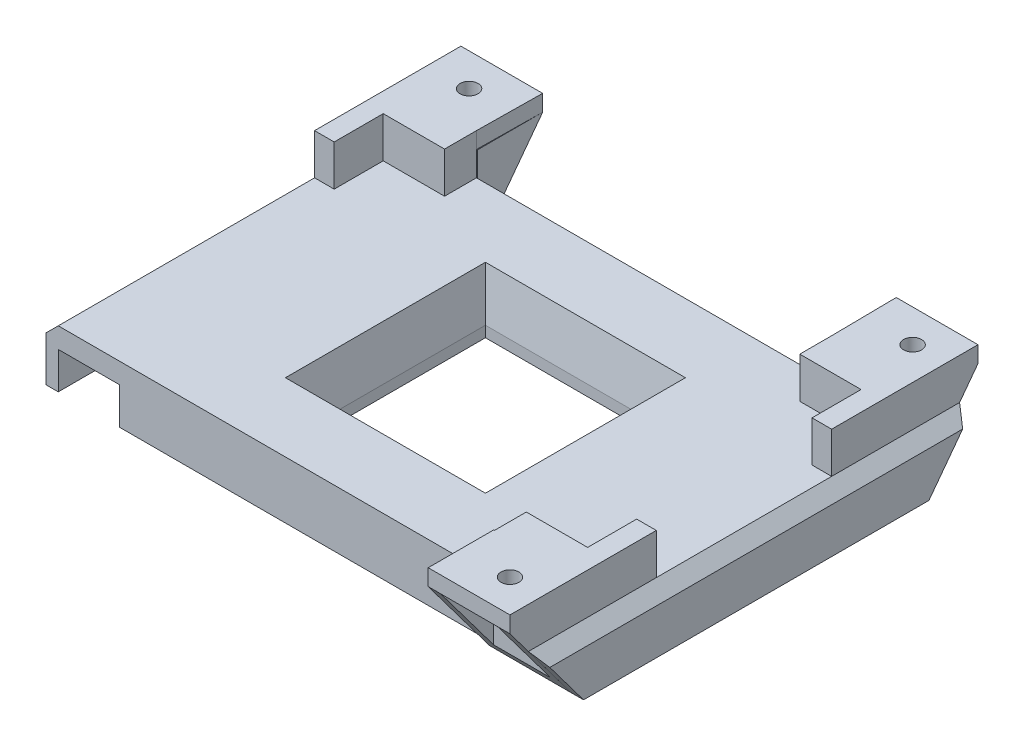
SolidWorks part; units mm, degrees
ref_plane "Спереди" through (0, 0, 0) normal (0, 0, 1) x (1, 0, 0)
ref_plane "Сверху" through (0, 0, 0) normal (0, 1, 0) x (1, 0, 0)
ref_plane "Справа" through (0, 0, 0) normal (1, 0, 0) x (0, 0, -1)
ref_plane "Плоскость4" through (0, 122.196, 0) normal (0, 1, 0) x (1, 0, 0)
sketch "Эскиз1" plane through (0, 122.196, 0) normal (0, 1, 0) x (1, 0, 0)
  line L0 (16.559, -48.2731) -> (16.559, -54.2731)
  line L1 (16.559, -54.2731) -> (7.559, -63.2731)
  line L2 (1.559, -63.2731) -> (7.559, -63.2731) construction
  line L3 (7.559, -63.2731) -> (1.559, -63.2731)
  line L4 (1.559, -63.2731) -> (1.559, -115.7731)
  line L5 (1.559, -115.7731) -> (7.559, -115.7731)
  line L6 (16.559, -124.7731) -> (7.559, -115.7731) construction
  line L7 (7.559, -115.7731) -> (1.559, -115.7731) construction
  line L8 (7.559, -115.7731) -> (16.559, -124.7731)
  line L9 (16.559, -124.7731) -> (16.559, -130.7731)
  line L10 (-8.25, -130.7731) -> (8.25, -130.7731) construction
  line L11 (16.559, -130.7731) -> (16.559, -124.7731) construction
  line L12 (16.559, -130.7731) -> (113.059, -130.7731)
  line L13 (113.059, -130.7731) -> (113.059, -124.7731)
  line L14 (113.059, -124.7731) -> (122.059, -115.7731)
  line L15 (122.059, -115.7731) -> (128.059, -115.7731)
  line L16 (128.059, -115.7731) -> (128.059, -63.2731)
  line L17 (128.059, -63.2731) -> (122.059, -63.2731)
  line L18 (122.059, -63.2731) -> (113.059, -54.2731)
  line L19 (113.059, -54.2731) -> (113.059, -48.2731)
  line L20 (113.059, -48.2731) -> (16.559, -48.2731)
  line L21 (42.3449, -67.059) -> (42.3449, -111.9872)
  line L22 (42.3449, -111.9872) -> (87.2731, -111.9872)
  line L23 (87.2731, -111.9872) -> (87.2731, -67.059)
  line L24 (87.2731, -67.059) -> (42.3449, -67.059)
extrude "Бобышка-Вытянуть1" add sketch "Эскиз1" along normal blind 9
ref_plane "Плоскость5" through (0, 131.196, 0) normal (0, 1, 0) x (1, 0, 0)
sketch "Эскиз2" plane through (0, 131.196, 0) normal (0, 1, 0) x (1, 0, 0)
  line L0 (128.059, -48.2731) -> (1.559, -48.2731)
  line L1 (1.559, -48.2731) -> (1.559, -130.7731)
  line L2 (1.559, -130.7731) -> (128.059, -130.7731)
  line L3 (-8.25, -130.7731) -> (8.25, -130.7731) construction
  line L4 (128.059, -130.7731) -> (128.059, -48.2731)
  line L5 (87.2731, -67.059) -> (87.2731, -111.9872)
  line L6 (87.2731, -111.9872) -> (87.2731, -67.059) construction
  line L7 (87.2731, -111.9872) -> (42.3449, -111.9872)
  line L8 (42.3449, -111.9872) -> (42.3449, -67.059)
  line L9 (42.3449, -67.059) -> (87.2731, -67.059)
extrude "Бобышка-Вытянуть2" add sketch "Эскиз2" along normal blind 5
chamfer "Фаска1" distance 2 angle 80 4 edges at (64.809, 136.196, 111.9872) (42.3449, 136.196, 89.5231) (87.2731, 136.196, 89.5231) (64.809, 136.196, 67.059) first distance on face at (64.809, 136.196, 89.5231)
ref_plane "Плоскость6" through (0, 136.196, 0) normal (0, 1, 0) x (1, 0, 0)
sketch "Эскиз3" plane through (0, 136.196, 0) normal (0, 1, 0) x (1, 0, 0)
  line L0 (128.059, -68.0731) -> (128.059, -48.2731)
  line L1 (128.059, -48.2731) -> (1.559, -48.2731) construction
  line L3 (21.359, -48.2731) -> (1.559, -48.2731)
  line L4 (1.559, -130.7731) -> (128.059, -130.7731) construction
  line L5 (1.559, -48.2731) -> (1.559, -130.7731) construction
  line L8 (128.059, -48.2731) -> (108.259, -48.2731)
  line L9 (6.359, -68.0731) -> (6.359, -56.0731)
  line L10 (6.359, -68.0731) -> (1.559, -68.0731)
  line L11 (1.559, -48.2731) -> (1.559, -68.0731)
  line L12 (6.359, -56.0731) -> (21.359, -56.0731)
  line L13 (21.359, -56.0731) -> (21.359, -48.2731)
  line L14 (108.259, -48.2731) -> (108.259, -56.0731)
  line L15 (108.259, -56.0731) -> (123.259, -56.0731)
  line L16 (128.059, -130.7731) -> (128.059, -48.2731) construction
  line L18 (128.059, -110.9731) -> (128.059, -130.7731)
  line L19 (128.059, -130.7731) -> (108.259, -130.7731)
  line L20 (108.259, -122.9731) -> (108.259, -130.7731)
  line L21 (108.259, -122.9731) -> (123.259, -122.9731)
  line L22 (123.259, -122.9731) -> (123.259, -110.9731)
  line L23 (123.259, -110.9731) -> (128.059, -110.9731)
  line L24 (123.259, -56.0731) -> (123.259, -68.0731)
  line L25 (123.259, -68.0731) -> (128.059, -68.0731)
extrude "Бобышка-Вытянуть3" add sketch "Эскиз3" along normal blind 10
ref_plane "Плоскость7" through (0, 146.196, 0) normal (0, 1, 0) x (1, 0, 0)
sketch "Эскиз4" plane through (0, 146.196, 0) normal (0, 1, 0) x (1, 0, 0)
  line L0 (128.059, -130.7731) -> (128.059, -146.7731)
  line L1 (128.059, -146.7731) -> (108.059, -146.7731)
  line L2 (108.059, -146.7731) -> (108.059, -130.7731)
  line L3 (108.259, -130.7731) -> (128.059, -130.7731) construction
  line L4 (128.059, -48.2731) -> (128.059, -32.2731)
  line L5 (128.059, -32.2731) -> (108.059, -32.2731)
  line L6 (108.059, -32.2731) -> (108.259, -48.2731)
  line L7 (1.559, -48.2731) -> (1.559, -32.2731)
  line L8 (1.559, -32.2731) -> (21.559, -32.2731)
  line L9 (21.559, -32.2731) -> (21.359, -48.2731)
  line L10 (21.359, -48.2731) -> (1.559, -48.2731)
  line L11 (108.259, -48.2731) -> (128.059, -48.2731)
  line L12 (108.059, -130.7731) -> (128.059, -130.7731)
  circle A0 centre (11.559, -40.2731) radius 2.2
  circle A1 centre (120.059, -138.7731) radius 2.2
  circle A2 centre (120.059, -40.2731) radius 2.2
extrude "Бобышка-Вытянуть4" add sketch "Эскиз4" against normal blind 4
ref_plane "Плоскость8" through (128.059, 0, 0) normal (1, 0, 0) x (0, 0, -1)
sketch "Эскиз5" plane through (128.059, 0, 0) normal (1, 0, 0) x (0, 0, -1)
  line L0 (-146.7731, 142.196) -> (-130.7731, 142.196)
  line L2 (-130.7731, 142.196) -> (-130.7731, 131.196)
  line L3 (-130.7731, 131.196) -> (-131.7731, 131.196)
  line L4 (-131.7731, 131.196) -> (-131.7731, 122.196)
  line L5 (45.375, 122.196) -> (-45.375, 122.196) construction
  line L6 (-146.7731, 142.196) -> (-131.7731, 122.196)
  line L7 (-32.2731, 142.196) -> (-48.2731, 142.196)
  line L8 (-48.2731, 142.196) -> (-48.2731, 131.196)
  line L9 (45.375, 131.196) -> (-45.375, 131.196) construction
  line L10 (-48.2731, 142.196) -> (-48.2731, 131.196) construction
  line L11 (-48.2731, 131.196) -> (-47.2731, 131.196)
  line L12 (-47.2731, 131.196) -> (-47.2731, 122.196)
  line L13 (-47.2731, 122.196) -> (-32.2731, 142.196)
extrude "Бобышка-Вытянуть5" add sketch "Эскиз5" against normal blind 20
ref_plane "Плоскость9" through (1.559, 0, 0) normal (-1, 0, 0) x (0, 0, 1)
sketch "Эскиз6" plane through (1.559, 0, 0) normal (-1, 0, 0) x (0, 0, 1)
  line L0 (48.2731, 142.196) -> (48.2731, 131.196)
  line L1 (45.375, 131.196) -> (-45.375, 131.196) construction
  line L2 (48.2731, 131.196) -> (47.2731, 131.196)
  line L3 (47.2731, 131.196) -> (47.7731, 131.196)
  line L4 (47.2731, 131.196) -> (47.2731, 122.196)
  line L5 (45.375, 122.196) -> (-45.375, 122.196) construction
  line L6 (47.2731, 122.196) -> (32.2731, 142.196)
  line L7 (32.2731, 142.196) -> (48.2731, 142.196)
extrude "Бобышка-Вытянуть6" add sketch "Эскиз6" against normal blind 20 contours L7 L6 L4 L2 L0 region at (1.559, 135.609, 42.6489)
ref_plane "Плоскость10" through (0, 122.196, 0) normal (0, -1, 0) x (-1, 0, 0)
sketch "Эскиз7" plane through (0, 122.196, 0) normal (0, -1, 0) x (-1, 0, 0)
  line L1 (-21.559, -32.2731) -> (-1.559, -32.2731) construction
  line L2 (-18.559, -32.2731) -> (-18.559, -45.2731)
  line L3 (-18.559, -45.2731) -> (-4.559, -45.2731)
  line L4 (-4.559, -45.2731) -> (-4.559, -32.2731)
  line L5 (-4.559, -32.2731) -> (-18.559, -32.2731)
  line L6 (-128.059, -32.2731) -> (-108.059, -32.2731) construction
  line L7 (-111.059, -32.2731) -> (-111.059, -45.2731)
  line L8 (-111.059, -45.2731) -> (-125.059, -45.2731)
  line L9 (-125.059, -45.2731) -> (-125.059, -32.2731)
  line L10 (-125.059, -32.2731) -> (-111.059, -32.2731)
  line L12 (-111.059, -146.7731) -> (-111.059, -133.7731)
  line L13 (-111.059, -133.7731) -> (-125.059, -133.7731)
  line L14 (-125.059, -133.7731) -> (-125.059, -146.7731)
  line L15 (-125.059, -146.7731) -> (-111.059, -146.7731)
extrude "Вырез-Вытянуть1" cut sketch "Эскиз7" against normal blind 20
sketch "Эскиз8" plane through (128.059, 0, 0) normal (1, 0, 0) x (0, 0, -1)
  line L1 (45.375, 122.196) -> (-45.375, 122.196) construction
  line L2 (45.375, 136.196) -> (-45.375, 136.196) construction
  line L3 (-142.2731, 136.196) -> (-36.7731, 136.196)
  line L4 (-47.2731, 122.196) -> (-32.2731, 142.196) construction
  line L5 (55.5784, 136.196) -> (-55.5784, 136.196) construction
  line L6 (-36.7731, 136.196) -> (-47.2731, 122.196)
  line L7 (-47.2731, 131.196) -> (-47.2731, 122.196) construction
  line L8 (-47.2731, 122.196) -> (-131.7685, 122.196)
  line L9 (-142.2731, 136.196) -> (-131.7685, 122.196)
  line L10 (-146.7731, 142.196) -> (-131.7731, 122.196) construction
extrude "Бобышка-Вытянуть7" add sketch "Эскиз8" along normal blind 3
sketch "Эскиз9" plane through (1.559, 0, 0) normal (-1, 0, 0) x (0, 0, 1)
  line L0 (47.2961, 122.196) -> (36.7731, 136.196)
  line L1 (-66.4206, 122.196) -> (66.4206, 122.196) construction
  line L2 (45.375, 122.196) -> (-45.375, 122.196) construction
  line L3 (45.375, 136.196) -> (-45.375, 136.196) construction
  line L4 (47.2731, 122.196) -> (32.2731, 142.196) construction
  line L5 (36.7731, 136.196) -> (130.7731, 136.196)
  line L6 (130.7731, 136.196) -> (130.7731, 122.196)
  line L7 (130.7731, 131.196) -> (130.7731, 122.196) construction
  line L8 (130.7731, 122.196) -> (47.2961, 122.196)
extrude "Бобышка-Вытянуть8" add sketch "Эскиз9" along normal blind 3
chamfer "Фаска2" distance 3 angle 45 2 edges at (131.059, 136.196, 89.5231) (-1.441, 136.196, 83.7731)
sketch "Эскиз10" plane through (0, 122.196, 0) normal (0, -1, 0) x (-1, 0, 0)
  line L0 (-128.059, -47.2731) -> (-129.059, -47.2731)
  line L1 (-128.059, 5.5) -> (-128.059, -5.5) construction
  line L2 (-131.059, -47.2731) -> (-128.059, -47.2731) construction
  line L3 (-129.059, -47.2731) -> (-129.059, -63.2731)
  line L4 (-129.059, -63.2731) -> (-128.059, -63.2731)
  line L5 (-128.059, -63.2731) -> (-122.059, -63.2731) construction
  line L6 (-128.059, -63.2731) -> (-128.059, -47.2731)
  line L7 (-128.059, -131.7685) -> (-128.059, -115.7731)
  line L8 (-128.059, -115.7731) -> (-129.059, -115.7731)
  line L9 (-129.059, -115.7731) -> (-129.059, -131.7685)
  line L10 (-131.059, -131.7685) -> (-128.059, -131.7685) construction
  line L11 (-129.059, -131.7685) -> (-128.059, -131.7685)
  line L12 (-1.559, -47.2731) -> (-1.559, -63.2731)
  line L13 (-1.559, -5.5) -> (-1.559, 5.5) construction
  line L14 (-21.559, -47.2731) -> (-1.559, -47.2731) construction
  line L15 (-1.559, -63.2731) -> (-0.559, -63.2731)
  line L16 (-0.559, -63.2731) -> (-0.559, -47.2961)
  line L17 (1.441, -47.2961) -> (-1.559, -47.2961) construction
  line L18 (-0.559, -47.2961) -> (-1.559, -47.2731)
extrude "Вырез-Вытянуть2" cut sketch "Эскиз10" against normal blind 9
